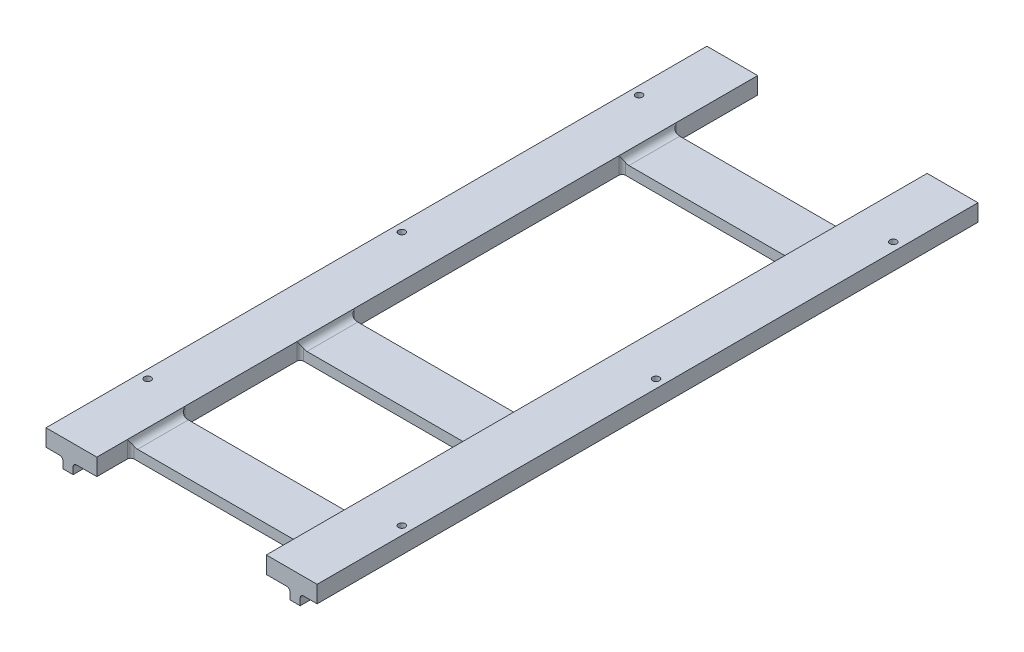
SolidWorks part; units mm, degrees
material "6061-T6 (SS)"
ref_plane "Front Plane" through (0, 0, 0) normal (0, 0, 1) x (1, 0, 0)
ref_plane "Top Plane" through (0, 0, 0) normal (0, 1, 0) x (1, 0, 0)
ref_plane "Right Plane" through (0, 0, 0) normal (1, 0, 0) x (0, 0, -1)
sketch "Sketch1" plane through (0, 0, 0) normal (0, 0, 1) x (1, 0, 0)
  line L1 (-5.7363, 0.5308) -> (9.2637, 0.5308)
  line L2 (9.2637, 0.5308) -> (9.2637, -1.4692)
  line L3 (9.2637, -1.4692) -> (59.2637, -1.4692)
  line L5 (66.2637, -4.4692) -> (2.2637, -4.4692)
  line L9 (-0.7363, -4.4692) -> (-5.7363, -4.4692)
  line L11 (-5.7363, 0.5308) -> (-5.7363, -4.4692)
  line L12 (34.2637, 10.4453) -> (34.2637, -24.0952) construction
  line L23 (66.2637, -7.4692) -> (66.2637, -4.4692)
  line L25 (69.2637, -4.4692) -> (69.2637, -7.4692)
  line L26 (74.2637, 0.5308) -> (74.2637, -4.4692)
  line L27 (69.2637, -4.4692) -> (74.2637, -4.4692)
  line L28 (59.2637, 0.5308) -> (59.2637, -1.4692)
  line L29 (74.2637, 0.5308) -> (59.2637, 0.5308)
  line L31 (-0.7363, -4.4692) -> (-0.7363, -7.4692)
  line L32 (-0.7363, -7.4692) -> (2.2637, -7.4692)
  line L33 (2.2637, -7.4692) -> (2.2637, -4.4692)
  line L34 (66.2637, -7.4692) -> (69.2637, -7.4692)
  point P18 (34.2637, -4.4692)
  point P19 (34.2637, -1.4692)
  dimension "D2" = 5
  dimension "D3" = 40
  dimension "D4" = 2
  dimension "D5" = 15
extrude "Boss-Extrude1" add sketch "Sketch1" along normal blind 190
sketch "Sketch2" plane through (0, -1.4692, 0) normal (0, 1, 0) x (1, 0, 0)
  line L0 (-49.7686, -100) -> (121.1591, -100) construction
  line L1 (59.2637, 0) -> (9.2637, 0) construction
  line L2 (59.2637, -190) -> (59.2637, 0) construction
  line L3 (9.2637, 0) -> (59.2637, 0)
  line L4 (9.2637, 0) -> (9.2637, -20)
  line L5 (9.2637, -20) -> (59.2637, -20)
  line L6 (59.2637, 0) -> (59.2637, -20)
  line L7 (9.2637, -180) -> (59.2637, -180)
  line L8 (59.2637, -200) -> (59.2637, -180)
  line L9 (9.2637, -200) -> (59.2637, -200)
  line L10 (9.2637, -200) -> (9.2637, -180)
  dimension "D1" = 100
  dimension "D2" = 20
extrude "Cut-Extrude1" cut sketch "Sketch2" against normal blind 50
sketch "Sketch3" plane through (0, -1.4692, 0) normal (0, 1, 0) x (1, 0, 0)
  line L0 (9.2637, -180) -> (9.2637, -20) construction
  line L1 (9.2637, -35) -> (59.2637, -35)
  line L2 (9.2637, -35) -> (9.2637, -115)
  line L3 (9.2637, -115) -> (59.2637, -115)
  line L4 (59.2637, -35) -> (59.2637, -115)
  line L5 (59.2637, -190) -> (59.2637, 0) construction
  line L6 (9.2637, -20) -> (59.2637, -20) construction
  dimension "D1" = 80
  dimension "D2" = 15
extrude "Cut-Extrude2" cut sketch "Sketch3" against normal blind 50
sketch "Sketch4" plane through (0, -1.4692, 0) normal (0, 1, 0) x (1, 0, 0)
  line L0 (9.2637, -180) -> (9.2637, -115) construction
  line L1 (9.2637, -130) -> (59.2637, -130)
  line L2 (9.2637, -130) -> (9.2637, -165)
  line L3 (9.2637, -165) -> (59.2637, -165)
  line L4 (59.2637, -130) -> (59.2637, -165)
  line L5 (59.2637, -190) -> (59.2637, 0) construction
  line L6 (59.2637, -180) -> (9.2637, -180) construction
  dimension "D1" = 35
  dimension "D2" = 15
ref_plane "Plane1" through (0, 0, 0) normal (0, 0, -1) x (-1, 0, 0)
extrude "Cut-Extrude4" cut sketch "Sketch4" against normal blind 50
sketch "Sketch5" plane through (0, -4.4692, 0) normal (0, -1, 0) x (-1, 0, 0)
  circle A0 centre (-71.7637, -162.5) radius 1
  circle A1 centre (3.2363, -162.5) radius 1
sketch "Sketch9" plane through (0, 0, 0) normal (0, 0, -1) x (-1, 0, 0)
  line L0 (-74.2637, 0.5308) -> (-59.2637, 0.5308)
  line L1 (-59.2637, 0.5308) -> (-59.2637, -4.4692)
  line L2 (-59.2637, -4.4692) -> (-74.2637, -4.4692)
  line L3 (-74.2637, -4.4692) -> (-74.2637, 0.5308)
  line L4 (-9.2637, 0.5308) -> (5.7363, 0.5308)
  line L5 (5.7363, 0.5308) -> (5.7363, -4.4692)
  line L6 (5.7363, 0.5308) -> (5.7363, -4.4692) construction
  line L7 (5.7363, -4.4692) -> (-9.2637, -4.4692)
  line L8 (-9.2637, -4.4692) -> (-9.2637, 0.5308)
extrude "Boss-Extrude4" add sketch "Sketch9" along normal blind 5
extrude "Cut-Extrude5" cut sketch "Sketch5" against normal blind 10
sketch "Sketch6" plane through (0, -4.4692, 0) normal (0, -1, 0) x (-1, 0, 0)
  circle A0 centre (3.2363, -87.5) radius 1
  circle A1 centre (3.2363, -17.5) radius 1
  circle A2 centre (-71.7637, -17.5) radius 1
  circle A3 centre (-71.7637, -87.5) radius 1
extrude "Cut-Extrude6" cut sketch "Sketch6" against normal blind 10 and the other way blind 100
fillet "Fillet1" radius 1 16 edges at (59.2637, -2.9692, 130) (59.2637, -2.9692, 180) (9.2637, -2.9692, 180) (9.2637, -2.9692, 130) (9.2637, -2.9692, 35) (59.2637, -2.9692, 35) (9.2637, -2.9692, 20) (59.2637, -2.9692, 20) (59.2637, -2.9692, 115) (9.2637, -2.9692, 115) (9.2637, -2.9692, 165) (59.2637, -2.9692, 165) (66.2637, -4.4692, 95) (-0.7363, -4.4692, 95) (2.2637, -4.4692, 95) (69.2637, -4.4692, 95)
fillet "Fillet2" radius 2 6 edges at (59.2637, -1.4692, 27.5) (9.2637, -1.4692, 27.5) (9.2637, -1.4692, 172.5) (59.2637, -1.4692, 172.5) (59.2637, -1.4692, 122.5) (9.2637, -1.4692, 122.5)
